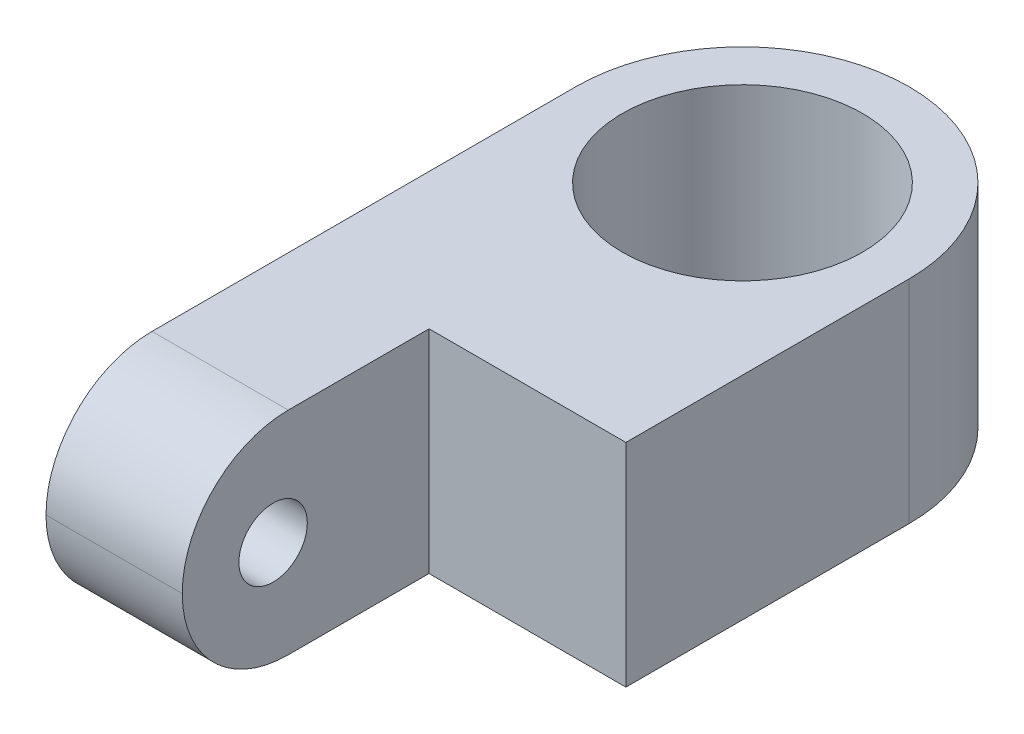
SolidWorks part; units mm, degrees
material "6063-O"
ref_plane "Front Plane" through (0, 0, 0) normal (0, 0, 1) x (1, 0, 0)
ref_plane "Top Plane" through (0, 0, 0) normal (0, 1, 0) x (1, 0, 0)
ref_plane "Right Plane" through (0, 0, 0) normal (1, 0, 0) x (0, 0, -1)
sketch "Sketch1" plane through (0, 0, 0) normal (1, 0, 0) x (0, 0, -1)
  line L1 (-11.5, 3.5) -> (11.5, 3.5)
  line L2 (-11.5, 3.5) -> (-11.5, -3.5)
  line L3 (-11.5, -3.5) -> (11.5, -3.5)
  line L4 (11.5, 3.5) -> (11.5, -3.5)
  point P4 (11.5, 0)
  point P6 (0, 3.5)
  dimension "D1" = 23
  dimension "D2" = 7
extrude "Boss-Extrude1" add sketch "Sketch1" along normal mid plane 11
sketch "Sketch2" plane through (0, 3.5, 0) normal (0, 1, 0) x (1, 0, 0)
  line L0 (5.5, 11.5) -> (-5.5, 11.5) construction
  circle A0 centre (0, 6) radius 3.9688
  dimension "D1" = 7.9375
  dimension "D2" = 5.5
extrude "Cut-Extrude1" cut sketch "Sketch2" against normal through all
sketch "Sketch3" plane through (5.5, 0, 0) normal (1, 0, 0) x (0, 0, -1)
  line L0 (-11.5, -3.5) -> (11.5, -3.5) construction
  line L1 (-11.5, 3.5) -> (-3.35, 3.5)
  line L2 (-11.5, 3.5) -> (-11.5, -3.5)
  line L3 (-11.5, -3.5) -> (-3.35, -3.5)
  line L4 (-3.35, 3.5) -> (-3.35, -3.5)
  dimension "D1" = 8.15
extrude "Cut-Extrude2" cut sketch "Sketch3" against normal blind 6.5
hole_wizard "#4-40 Tapped Hole1" positions "Sketch5" profile "Sketch6" tap size "#4-40" standard "ANSI Inch" end condition through all
sketch "Sketch5" plane through (-1, 0, 0) normal (1, 0, 0) x (0, 0, -1)
  line L0 (-3.35, 3.5) -> (-11.5, 3.5) construction
  line L2 (11.5, -3.5) -> (11.5, 3.5) construction
  point P0 (-8.5, -0.04)
  dimension "D1" = 3.54
  dimension "D2" = 20
sketch "Sketch6" plane through (-1, -0.04, 8.5) normal (0, 1, 0) x (0, 0, -1)
  line L0 (0, 0) -> (0, 4.5)
  line L1 (0, 4.5) -> (1.1303, 4.5)
  line L2 (1.1303, 4.5) -> (1.1303, 0)
  line L5 (1.1303, 0) -> (0, 0)
  line L11 (0, -6.35) -> (0, 107.95) construction
  dimension "Thru Tap Drill Dia." = 2.2606
  dimension "Thru Tap Drill Depth" = 4.5
cosmetic thread "Hole Thread1"
fillet "Fillet1" radius 3.5 2 edges at (-3.25, -3.5, 11.5) (-3.25, 3.5, 11.5)
fillet "Fillet2" radius 5.5 2 edges at (-5.5, 0, -11.5) (5.5, 0, -11.5)
